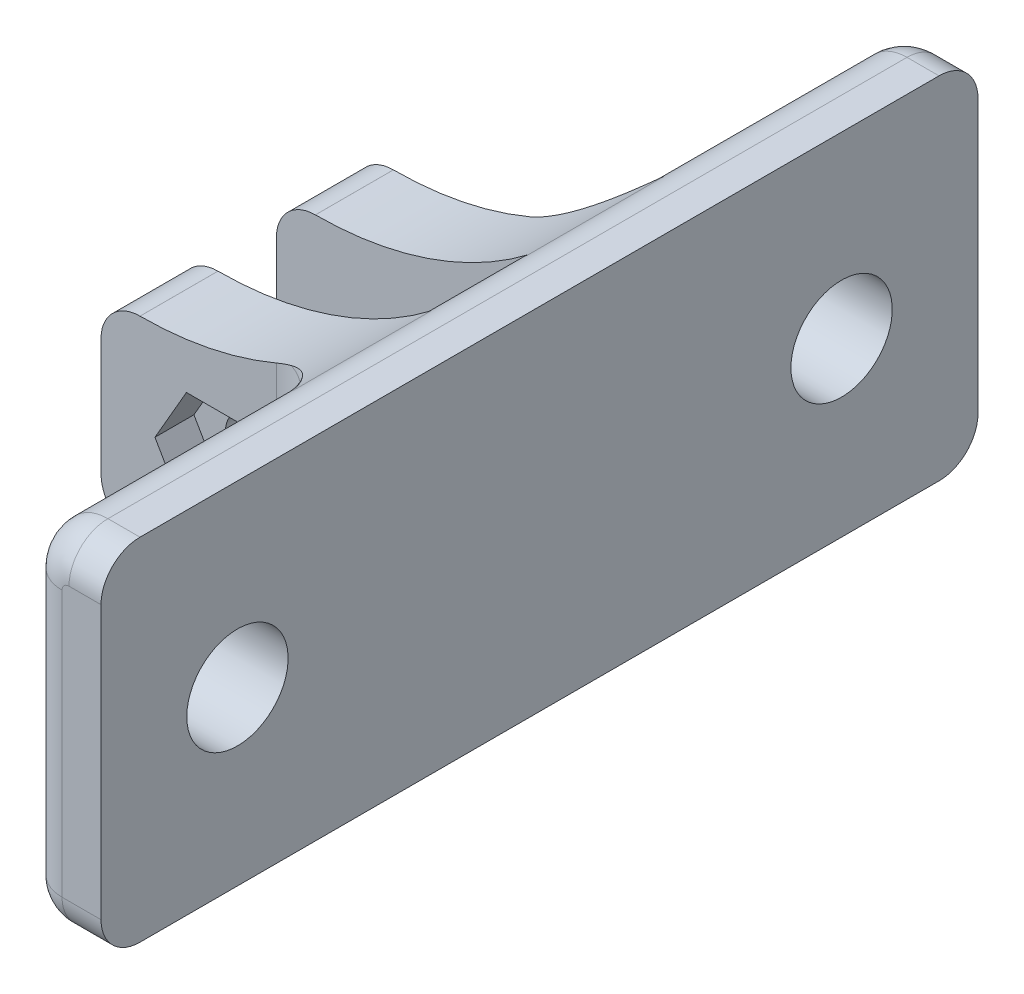
SolidWorks part; units mm, degrees
ref_plane "Front Plane" through (0, 0, 0) normal (0, 0, 1) x (1, 0, 0)
ref_plane "Top Plane" through (0, 0, 0) normal (0, 1, 0) x (1, 0, 0)
ref_plane "Right Plane" through (0, 0, 0) normal (1, 0, 0) x (0, 0, -1)
sketch "Sketch5" plane through (0, 0, 0) normal (0, 0, 1) x (1, 0, 0)
  line L0 (4, 0) -> (4, 18)
  line L1 (2, 0) -> (4, 0)
  line L2 (0, 2) -> (0, 15.6436)
  line L8 (2.3564, 18) -> (4, 18)
  arc A0 (0, 2) -> (2, 0) centre (2, 2) ccw
  arc A3 (2.3564, 18) -> (0, 15.6436) centre (2.3564, 15.6436) ccw
  point P1 (0, 0)
  point P11 (0, 0)
  dimension "D5" = 2
  dimension "D1" = 4
  dimension "D2" = 18
extrude "Boss-Extrude5" add sketch "Sketch5" along normal blind 45
sketch "Sketch6" plane through (0, 0, 0) normal (-1, 0, 0) x (0, 0, 1)
  line L0 (45, 15.6436) -> (0, 15.6436) construction
  line L1 (20, 13.8218) -> (25, 13.8218) construction
  line L2 (20, 13.8218) -> (20, 3.8218)
  line L3 (20, 3.8218) -> (25, 3.8218) construction
  line L4 (25, 13.8218) -> (25, 3.8218)
  line L6 (20, 13.8218) -> (16, 13.8218)
  line L7 (16, 13.8218) -> (16, 3.8218)
  line L8 (16, 3.8218) -> (20, 3.8218)
  line L9 (25, 3.8218) -> (29, 3.8218)
  line L11 (29, 3.8218) -> (29, 13.8218)
  line L12 (29, 13.8218) -> (25, 13.8218)
  line L13 (45, 15.6436) -> (45, 2) construction
  point P4 (22.5, 13.8218)
  point P7 (22.5, 15.6436)
  point P10 (45, 8.8218)
  point P11 (26.229, 3.8218)
  point P12 (29, 8.8218)
  point P16 (16, 8.8218)
  dimension "D1" = 5
  dimension "D2" = 10
  dimension "D3" = 4
extrude "Boss-Extrude6" add sketch "Sketch6" along normal blind 12
sketch "Sketch7" plane through (0, 0, 29) normal (0, 0, 1) x (1, 0, 0)
  line L0 (-12, 3.8218) -> (-12, 13.8218) construction
  line L1 (-2.7668, 8.8218) -> (-4.3834, 11.6218)
  line L2 (-4.3834, 11.6218) -> (-7.6166, 11.6218)
  line L3 (-7.6166, 11.6218) -> (-9.2332, 8.8218)
  line L4 (-9.2332, 8.8218) -> (-7.6166, 6.0218)
  line L5 (-7.6166, 6.0218) -> (-4.3834, 6.0218)
  line L6 (-4.3834, 6.0218) -> (-2.7668, 8.8218)
  circle A0 centre (-6, 8.8218) radius 2.8 construction
  circle A1 centre (-6, 8.8218) radius 1.625
  point P11 (-12, 8.8218)
  dimension "D1" = 5.6
  dimension "D3" = 3.25
  dimension "D2" = 6
extrude "Cut-Extrude1" cut sketch "Sketch7" against normal blind 2
extrude "Cut-Extrude2" cut sketch "Sketch7<2>" against normal through all contours A1 region at (-6, 8.8218, 29)
sketch "Sketch7<2>" plane through (0, 0, 29) normal (0, 0, 1) x (1, 0, 0) same geometry as "Sketch7"
fillet "Fillet3" radius 2 4 edges at (-12, 3.8218, 27) (-12, 3.8218, 18) (-12, 13.8218, 27) (-12, 13.8218, 18)
fillet "Fillet4" radius 18 4 edges at (0, 13.8218, 18) (0, 13.8218, 27) (0, 3.8218, 27) (0, 3.8218, 18)
fillet "Fillet5" radius 3 6 edges at (0.2442, 16.6882, 16) (0.2179, 1.0922, 16) (0.2179, 1.0922, 29) (0.2442, 16.6882, 29) (0, 8.8218, 16) (0, 8.8218, 29)
sketch "Sketch8" plane through (0, 0, 0) normal (-1, 0, 0) x (0, 0, 1)
  line L0 (7, 8.8218) -> (38, 8.8218) construction
  line L1 (45, 15.6436) -> (45, 2) construction
  line L2 (45, 18) -> (0, 18) construction
  line L3 (0, 15.6436) -> (0, 2) construction
  circle A0 centre (7, 8.8218) radius 2.6
  circle A1 centre (38, 8.8218) radius 2.6
  point P4 (45, 8.8218)
  point P7 (22.5, 8.8218)
  point P10 (22.5, 18)
  point P13 (0, 8.8218)
  dimension "D1" = 5.2
  dimension "D2" = 7
extrude "Cut-Extrude3" cut sketch "Sketch8" against normal blind 10
fillet "Fillet6" radius 2 10 edges at (3, 0, 0) (0.5858, 0.5858, 0) (0, 8.8218, 0) (0.6902, 17.3098, 0) (3, 0, 45) (0.5858, 0.5858, 45) (0, 8.8218, 45) (0.6902, 17.3098, 45) (3.1782, 18, 0) (3.1782, 18, 45)
